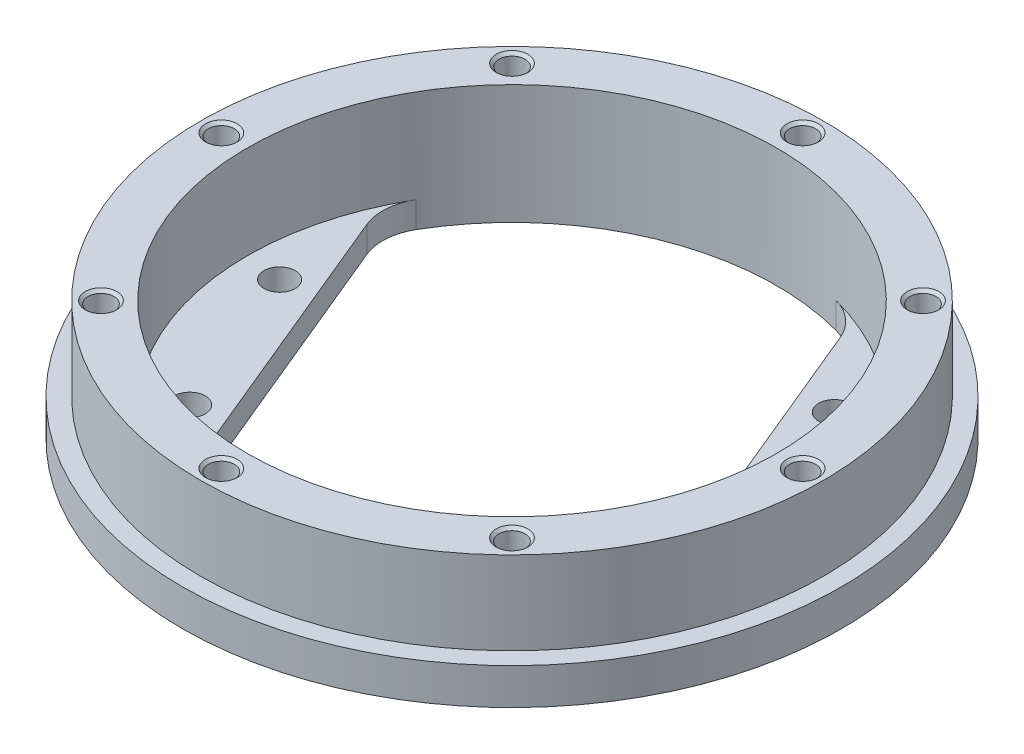
SolidWorks part; units mm, degrees
material "6061-T6 (SS)"
ref_plane "前视基准面" through (0, 0, 0) normal (0, 0, 1) x (1, 0, 0)
ref_plane "上视基准面" through (0, 0, 0) normal (0, 1, 0) x (1, 0, 0)
ref_plane "右视基准面" through (0, 0, 0) normal (1, 0, 0) x (0, 0, -1)
sketch "草图1" plane through (0, 0, 0) normal (0, 1, 0) x (1, 0, 0)
  circle A0 centre (0, 0) radius 30
  circle A1 centre (0, 0) radius 25.5
  dimension "D1" = 60
  dimension "D2" = 4.5
extrude "凸台-拉伸1" add sketch "草图1" along normal blind 8
sketch "草图2" plane through (0, 0, 0) normal (0, -1, 0) x (1, 0, 0)
  circle A0 centre (0, 0) radius 31.75
  circle A1 centre (0, 0) radius 25.5
  circle A2 centre (0, 0) radius 25.5 construction
  dimension "D1" = 63.5
extrude "凸台-拉伸2" add sketch "草图2" along normal blind 3.5
sketch "草图4" plane through (0, 8, 0) normal (0, 1, 0) x (1, 0, 0)
  line L0 (0, 28) -> (0, 0) construction
  circle A0 centre (0, 28) radius 1.25
  circle A1 centre (19.799, 19.799) radius 1.25
  circle A2 centre (28, 0) radius 1.25
  circle A3 centre (19.799, -19.799) radius 1.25
  circle A4 centre (0, -28) radius 1.25
  circle A5 centre (-19.799, -19.799) radius 1.25
  circle A6 centre (-28, 0) radius 1.25
  circle A7 centre (-19.799, 19.799) radius 1.25
  circle A8 centre (0, 0) radius 28 construction
  point P12 (0, 0)
  dimension "D2" = 2.5
  dimension "D1" = 56
  dimension "D3" = 8
extrude "切除-拉伸1" cut sketch "草图4" against normal through all
cosmetic thread "孔螺蚊线1" parameters "D2"=3
cosmetic thread "孔螺蚊线2" parameters "D2"=3
cosmetic thread "孔螺蚊线3" parameters "D2"=3
cosmetic thread "孔螺蚊线4" parameters "D2"=3
cosmetic thread "孔螺蚊线5" parameters "D2"=3
cosmetic thread "孔螺蚊线6" parameters "D2"=3
cosmetic thread "孔螺蚊线7" parameters "D2"=3
cosmetic thread "孔螺蚊线8" parameters "D2"=3
hole_wizard "M3 螺纹孔1" positions "3D草图1" profile "草图5" tap size "M3" standard "ISO" end condition through all
sketch3d "3D草图1"
  line L0 (0, -3.5, -28) -> (0, 8, -28) construction
  line L1 (19.799, -3.5, -19.799) -> (19.799, 8, -19.799) construction
  line L2 (28, -3.5, 0) -> (28, 8, 0) construction
  line L3 (19.799, -3.5, 19.799) -> (19.799, 8, 19.799) construction
  line L4 (0, -3.5, 28) -> (0, 8, 28) construction
  line L5 (-19.799, -3.5, 19.799) -> (-19.799, 8, 19.799) construction
  line L6 (-28, -3.5, 0) -> (-28, 8, 0) construction
  line L7 (-19.799, -3.5, -19.799) -> (-19.799, 8, -19.799) construction
  point P0 (0, 8, -28)
  point P4 (19.799, 8, -19.799)
  point P8 (28, 8, 0)
  point P12 (19.799, 8, 19.799)
  point P16 (0, 8, 28)
  point P20 (-19.799, 8, 19.799)
  point P24 (-28, 8, 0)
  point P28 (-19.799, 8, -19.799)
sketch "草图5" plane through (0, 8, -28) normal (1, 0, 0) x (0, 0, 1)
  line L0 (0, 0) -> (0, 11.5)
  line L1 (0, 11.5) -> (1.25, 11.5)
  line L2 (1.25, 11.5) -> (1.25, 0.275)
  line L3 (1.25, 0.275) -> (1.525, 0)
  line L5 (1.525, 0) -> (0, 0)
  line L6 (-1.25, 0.275) -> (-1.525, 0) construction
  line L11 (0, -6.35) -> (0, 107.95) construction
  dimension "通孔螺纹孔钻头直径" = 2.5
  dimension "通孔螺纹孔钻头深度" = 11.5
  dimension "近端锥形沉头孔直径" = 3.05
  dimension "近端锥形沉头孔角度" = 90
sketch "草图6" plane through (0, -3.5, 0) normal (0, -1, 0) x (1, 0, 0)
  line L0 (-23.2374, -10.5011) -> (-9.006, 23.8567)
  line L1 (-15.8319, 15.2169) -> (-21.9548, 0.4348) construction
  line L2 (-18.8933, 7.8259) -> (0, 0) construction
  line L3 (0, 0) -> (-3.8623, -9.3244) construction
  line L4 (9.006, -23.8567) -> (23.2374, 10.5011)
  line L5 (0, 0) -> (-12.4621, 0) construction
  circle A0 centre (0, 0) radius 25.5 construction
  arc A1 (-9.006, 23.8567) -> (-23.2374, -10.5011) centre (0, 0) ccw
  circle A2 centre (-21.9548, 0.4348) radius 1.5
  circle A3 centre (-15.8319, 15.2169) radius 1.5
  circle A4 centre (21.9548, -0.4348) radius 1.5
  circle A5 centre (15.8319, -15.2169) radius 1.5
  arc A6 (23.2374, 10.5011) -> (9.006, -23.8567) centre (0, 0) cw
  dimension "D2" = 3
  dimension "D1" = 16
  dimension "D3" = 40.9
  dimension "D4" = 3
  dimension "D5" = 22.5
extrude "凸台-拉伸3" add sketch "草图6" against normal blind 2.5
fillet "圆角1" radius 5 4 edges at (-9.006, -2.25, 23.8567) (-23.2374, -2.25, -10.5011) (9.006, -2.25, -23.8567) (23.2374, -2.25, 10.5011)
